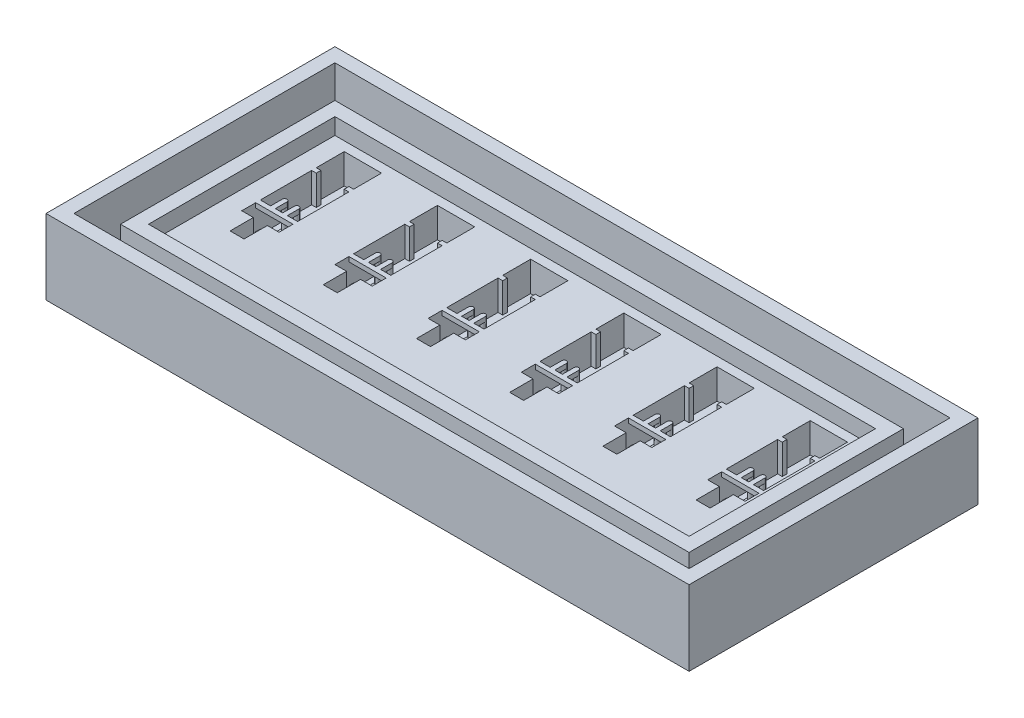
SolidWorks part; units mm, degrees
ref_plane "Front Plane" through (0, 0, 0) normal (0, 0, 1) x (1, 0, 0)
ref_plane "Top Plane" through (0, 0, 0) normal (0, 1, 0) x (1, 0, 0)
ref_plane "Right Plane" through (0, 0, 0) normal (1, 0, 0) x (0, 0, -1)
sketch "Sketch1" plane through (0, 0, 0) normal (0, 1, 0) x (1, 0, 0)
  line L1 (-30.5, -11.5) -> (30.5, -11.5)
  line L2 (-30.5, -11.5) -> (-30.5, 11.5)
  line L3 (-30.5, 11.5) -> (30.5, 11.5)
  line L4 (30.5, -11.5) -> (30.5, 11.5)
  line L5 (-30.5, -11.5) -> (30.5, 11.5) construction
  line L6 (-30.5, 11.5) -> (30.5, -11.5) construction
  point P0 (0, 0)
  dimension "D1" = 61
  dimension "D2" = 23
extrude "Boss-Extrude1" add sketch "Sketch1" along normal blind 6.05
sketch "Sketch2" plane through (0, 6.05, 0) normal (0, 1, 0) x (1, 0, 0)
  line L1 (29, -10) -> (-29, -10)
  line L2 (29, -10) -> (29, 10)
  line L3 (29, 10) -> (-29, 10)
  line L4 (-29, -10) -> (-29, 10)
  line L5 (29, -10) -> (-29, 10) construction
  line L6 (29, 10) -> (-29, -10) construction
  point P0 (0, 0)
  dimension "D1" = 58
  dimension "D2" = 20
extrude "Cut-Extrude1" cut sketch "Sketch2" against normal blind 1.75
sketch "Sketch4" plane through (0, 4.3, 0) normal (0, 1, 0) x (1, 0, 0)
  line L0 (-29, 0) -> (-28, 0) construction
  line L2 (29, -10) -> (29, 10) construction
  line L3 (-23, -0.5) -> (-22, -0.5)
  line L4 (-27, -9) -> (-23, -9)
  line L5 (-27, -9) -> (-27, -1.5)
  line L6 (-27, 9) -> (-23, 9)
  line L7 (-23, -9) -> (-23, -1.5)
  line L8 (-17, -9) -> (-13, -9)
  line L9 (-13, -9) -> (-13, -1.5)
  line L10 (-28, -1.5) -> (-27, -1.5)
  line L11 (-28, -1.5) -> (-28, -0.5)
  line L12 (-28, -0.5) -> (-27, -0.5)
  line L13 (-22, -1.5) -> (-22, -0.5)
  line L14 (-23, -1.5) -> (-22, -1.5)
  line L15 (-23, -0.5) -> (-23, 9)
  line L16 (-13, -1.5) -> (-12, -1.5)
  line L17 (-23, 0) -> (29, 0) construction
  line L18 (-12, -1.5) -> (-12, -0.5)
  line L19 (-27, -0.5) -> (-27, 9)
  line L20 (-13, -0.5) -> (-12, -0.5)
  line L21 (-13, -0.5) -> (-13, 9)
  line L22 (-17, 9) -> (-13, 9)
  line L23 (-17, -0.5) -> (-17, 9)
  line L24 (-18, -0.5) -> (-17, -0.5)
  line L25 (-18, -1.5) -> (-18, -0.5)
  line L26 (-18, -1.5) -> (-17, -1.5)
  line L27 (-17, -9) -> (-17, -1.5)
  line L28 (-7, -9) -> (-3, -9)
  line L29 (-3, -9) -> (-3, -1.5)
  line L30 (-3, -1.5) -> (-2, -1.5)
  line L31 (-2, -1.5) -> (-2, -0.5)
  line L32 (-3, -0.5) -> (-2, -0.5)
  line L33 (-3, -0.5) -> (-3, 9)
  line L34 (-7, 9) -> (-3, 9)
  line L35 (-7, -0.5) -> (-7, 9)
  line L36 (-8, -0.5) -> (-7, -0.5)
  line L37 (-8, -1.5) -> (-8, -0.5)
  line L38 (-8, -1.5) -> (-7, -1.5)
  line L39 (-7, -9) -> (-7, -1.5)
  line L40 (3, -9) -> (7, -9)
  line L41 (7, -9) -> (7, -1.5)
  line L42 (7, -1.5) -> (8, -1.5)
  line L43 (8, -1.5) -> (8, -0.5)
  line L44 (7, -0.5) -> (8, -0.5)
  line L45 (7, -0.5) -> (7, 9)
  line L46 (3, 9) -> (7, 9)
  line L47 (3, -0.5) -> (3, 9)
  line L48 (2, -0.5) -> (3, -0.5)
  line L49 (2, -1.5) -> (2, -0.5)
  line L50 (2, -1.5) -> (3, -1.5)
  line L51 (3, -9) -> (3, -1.5)
  line L52 (13, -9) -> (17, -9)
  line L53 (17, -9) -> (17, -1.5)
  line L54 (17, -1.5) -> (18, -1.5)
  line L55 (18, -1.5) -> (18, -0.5)
  line L56 (17, -0.5) -> (18, -0.5)
  line L57 (17, -0.5) -> (17, 9)
  line L58 (13, 9) -> (17, 9)
  line L59 (13, -0.5) -> (13, 9)
  line L60 (12, -0.5) -> (13, -0.5)
  line L61 (12, -1.5) -> (12, -0.5)
  line L62 (12, -1.5) -> (13, -1.5)
  line L63 (13, -9) -> (13, -1.5)
  line L64 (23, -9) -> (27, -9)
  line L65 (27, -9) -> (27, -1.5)
  line L66 (27, -1.5) -> (28, -1.5)
  line L67 (28, -1.5) -> (28, -0.5)
  line L68 (27, -0.5) -> (28, -0.5)
  line L69 (27, -0.5) -> (27, 9)
  line L70 (23, 9) -> (27, 9)
  line L71 (23, -0.5) -> (23, 9)
  line L72 (22, -0.5) -> (23, -0.5)
  line L73 (22, -1.5) -> (22, -0.5)
  line L74 (22, -1.5) -> (23, -1.5)
  line L75 (23, -9) -> (23, -1.5)
  line L76 (-27, -9) -> (-17, -9) construction
  line L77 (-25, 9) -> (-25, -9) construction
  line L78 (-29, 10) -> (-29, -10) construction
  point P6 (3, 0)
  point P11 (3, 0)
  point P85 (-25, 0)
  dimension "D1" = 4
  dimension "D2" = 18
  dimension "D3" = 6
  dimension "D4" = 1
  dimension "D6" = 10
  dimension "D7" = 1
  dimension "D8" = 9.5
  dimension "D5" = 6
extrude "Cut-Extrude3" cut sketch "Sketch4" against normal blind 3.2
sketch "Sketch5" plane through (0, 1.1, 0) normal (0, 1, 0) x (1, 0, 0)
  line L1 (-28, -0.5) -> (-22, -0.5)
  line L2 (-28, -0.5) -> (-28, -1.5)
  line L3 (-28, -1.5) -> (-22, -1.5)
  line L4 (-22, -0.5) -> (-22, -1.5)
  line L5 (-18, -0.5) -> (-12, -0.5)
  line L6 (-18, -0.5) -> (-18, -1.5)
  line L7 (-18, -1.5) -> (-12, -1.5)
  line L8 (-12, -0.5) -> (-12, -1.5)
  line L9 (-8, -0.5) -> (-2, -0.5)
  line L10 (-8, -0.5) -> (-8, -1.5)
  line L11 (-8, -1.5) -> (-2, -1.5)
  line L12 (-2, -0.5) -> (-2, -1.5)
  line L13 (2, -0.5) -> (8, -0.5)
  line L14 (2, -0.5) -> (2, -1.5)
  line L15 (2, -1.5) -> (8, -1.5)
  line L16 (8, -0.5) -> (8, -1.5)
  line L17 (12, -0.5) -> (18, -0.5)
  line L18 (12, -0.5) -> (12, -1.5)
  line L19 (12, -1.5) -> (18, -1.5)
  line L20 (18, -0.5) -> (18, -1.5)
  line L21 (22, -0.5) -> (28, -0.5)
  line L22 (22, -0.5) -> (22, -1.5)
  line L23 (22, -1.5) -> (28, -1.5)
  line L24 (28, -0.5) -> (28, -1.5)
extrude "Cut-Extrude4" cut sketch "Sketch5" against normal blind 0.5
sketch "Sketch10" plane through (0, 4.3, 0) normal (0, 1, 0) x (1, 0, 0)
  line L0 (-3, -0.5) -> (-3, 9) construction
  line L1 (-7, -0.5) -> (-3, -0.5)
  line L2 (-7, -0.5) -> (-7, 0)
  line L3 (-7, 0) -> (-3, 0)
  line L6 (-3, 0) -> (-3, -0.5)
  line L7 (23, 9) -> (23, -0.5) construction
  line L8 (23, 0) -> (27, 0)
  line L9 (23, 0) -> (23, -0.5)
  line L10 (23, -0.5) -> (27, -0.5)
  line L11 (27, 0) -> (27, -0.5)
  line L12 (27, -0.5) -> (27, 9) construction
  line L13 (13, 9) -> (13, -0.5) construction
  line L14 (13, 0) -> (17, 0)
  line L15 (13, 0) -> (13, -0.5)
  line L16 (13, -0.5) -> (17, -0.5)
  line L17 (17, 0) -> (17, -0.5)
  line L18 (17, -0.5) -> (17, 9) construction
  line L19 (3, 9) -> (3, -0.5) construction
  line L20 (3, 0) -> (7, 0)
  line L21 (3, 0) -> (3, -0.5)
  line L22 (3, -0.5) -> (7, -0.5)
  line L23 (7, 0) -> (7, -0.5)
  line L24 (7, -0.5) -> (7, 9) construction
  line L25 (-17, 9) -> (-17, -0.5) construction
  line L26 (-17, 0) -> (-13, 0)
  line L27 (-17, 0) -> (-17, -0.5)
  line L28 (-17, -0.5) -> (-13, -0.5)
  line L29 (-13, 0) -> (-13, -0.5)
  line L30 (-13, -0.5) -> (-13, 9) construction
  line L31 (-27, 9) -> (-27, -0.5) construction
  line L32 (-27, 0) -> (-23, 0)
  line L33 (-27, 0) -> (-27, -0.5)
  line L34 (-27, -0.5) -> (-23, -0.5)
  line L35 (-23, 0) -> (-23, -0.5)
  line L36 (-23, -0.5) -> (-23, 9) construction
  dimension "D1" = 0.5
extrude "Boss-Extrude3" add sketch "Sketch10" against normal blind 0.5
sketch "Sketch11" plane through (0, 1.1, 0) normal (0, 1, 0) x (1, 0, 0)
  line L0 (-3, -0.5) -> (-3, 9) construction
  line L1 (-7, -0.5) -> (-3, -0.5)
  line L2 (-7, -0.5) -> (-7, 0)
  line L3 (-7, 0) -> (-3, 0)
  line L5 (13, 9) -> (13, 0) construction
  line L6 (-3, 0) -> (-3, -0.5)
  line L7 (-27, 9) -> (-27, -0.5) construction
  line L8 (-27, 0) -> (-23, 0)
  line L9 (-27, 0) -> (-27, -0.5)
  line L10 (-27, -0.5) -> (-23, -0.5)
  line L11 (-23, 0) -> (-23, -0.5)
  line L12 (-23, 0) -> (-23, 9) construction
  line L13 (-17, 9) -> (-17, -0.5) construction
  line L14 (-17, 0) -> (-13, 0)
  line L15 (-17, 0) -> (-17, -0.5)
  line L16 (-17, -0.5) -> (-13, -0.5)
  line L17 (-13, 0) -> (-13, -0.5)
  line L18 (-13, 0) -> (-13, 9) construction
  line L19 (28, -0.5) -> (22, -0.5) construction
  line L24 (3, 9) -> (3, 0) construction
  line L25 (3, 0) -> (7, 0)
  line L26 (3, 0) -> (3, -0.5)
  line L27 (3, -0.5) -> (7, -0.5)
  line L28 (7, 0) -> (7, -0.5)
  line L29 (7, -0.5) -> (7, 9) construction
  line L30 (13, 0) -> (17, 0)
  line L31 (13, 0) -> (13, -0.5)
  line L32 (13, -0.5) -> (17, -0.5)
  line L33 (17, 0) -> (17, -0.5)
  line L34 (17, 0) -> (17, 9) construction
  line L35 (23, 0) -> (27, 0)
  line L36 (23, 0) -> (23, -0.5)
  line L37 (23, -0.5) -> (27, -0.5)
  line L38 (27, 0) -> (27, -0.5)
  line L39 (27, 0) -> (27, 9) construction
  dimension "D1" = 0.5
extrude "Boss-Extrude4" add sketch "Sketch11" along normal blind 0.5
sketch "Sketch9" plane through (0, 1.1, 0) normal (0, 1, 0) x (1, 0, 0)
  line L0 (-23, 0) -> (-27, 0) construction
  line L1 (-5.9, 1.25) -> (-5.4, 1.25)
  line L2 (-5.9, 1.25) -> (-5.9, 0)
  line L3 (-5.9, 0) -> (-5.4, 0)
  line L4 (-5.4, 1.25) -> (-5.4, 0)
  line L5 (-25.75, 0) -> (-25.25, 0)
  line L6 (-4.6, 1.25) -> (-4.1, 1.25)
  line L7 (-4.6, 1.25) -> (-4.6, 0)
  line L8 (-4.6, 0) -> (-4.1, 0)
  line L9 (-4.1, 1.25) -> (-4.1, 0)
  line L10 (-3, 0) -> (-7, 0) construction
  line L11 (-4.6, 0.625) -> (-5.4, 0.625) construction
  line L12 (-5.4, 0.625) -> (-5, 0.625) construction
  line L13 (-5, 0.625) -> (-5, 0) construction
  line L14 (-25.75, 0) -> (-25.75, 1.25)
  line L15 (-25.75, 1.25) -> (-25.25, 1.25)
  line L16 (-25.25, 0) -> (-25.25, 1.25)
  line L17 (-23, 0) -> (-27, 0) construction
  line L18 (-24.75, 0) -> (-24.25, 0)
  line L19 (-24.75, 0) -> (-24.75, 1.25)
  line L20 (-24.75, 1.25) -> (-24.25, 1.25)
  line L21 (-24.25, 0) -> (-24.25, 1.25)
  line L22 (17, 0) -> (13, 0) construction
  line L23 (13.95, 0) -> (14.45, 0)
  line L24 (13.95, 0) -> (13.95, 1.25)
  line L25 (13.95, 1.25) -> (14.45, 1.25)
  line L26 (14.45, 0) -> (14.45, 1.25)
  line L27 (-25.25, 0.625) -> (-24.75, 0.625) construction
  line L28 (15.55, 0) -> (16.05, 0)
  line L29 (15.55, 0) -> (15.55, 1.25)
  line L30 (15.55, 1.25) -> (16.05, 1.25)
  line L31 (16.05, 0) -> (16.05, 1.25)
  line L32 (-24.75, 0.625) -> (-25, 0.625) construction
  line L33 (-25, 0.625) -> (-25, 0) construction
  line L34 (14.45, 0.625) -> (15.55, 0.625) construction
  line L35 (15.55, 0.625) -> (15, 0.625) construction
  line L36 (15, 0.625) -> (15, 0) construction
  line L37 (17, 0) -> (13, 0) construction
  circle A0 centre (-4.35, 1.25) radius 0.25
  circle A1 centre (-5.65, 1.25) radius 0.25
  circle A2 centre (-25.5, 1.25) radius 0.25
  circle A3 centre (-24.5, 1.25) radius 0.25
  circle A4 centre (14.2, 1.25) radius 0.25
  circle A5 centre (15.8, 1.25) radius 0.25
  dimension "D1" = 0.5
  dimension "D2" = 1.25
  dimension "D3" = 0.8
  dimension "D4" = 0.5
  dimension "D5" = 1.1
extrude "Boss-Extrude5" add sketch "Sketch9" along normal up to surface (0.5 mm away) contours A3 L19 L18 L21 | A2 L14 L5 L16 | L15 A2 | L15 A2 | A5 L29 L28 L31 | L30 A5 | L30 A5 | L25 A4 | L25 A4 | A4 L24 L23 L26 | L2 L1 L4 L3 | A1 | A0 | L7 L6 L9 L8 | A3 region at (-25.5, 1.1, -0.5283) region at (-25.5, 1.1, -1.3561) region at (-25.5, 1.1, -1.1439) region at (-24.5, 1.1, -0.5283) region at (14.2, 1.1, -0.5283) region at (14.2, 1.1, -1.3561) region at (14.2, 1.1, -1.1439) region at (15.8, 1.1, -0.5283) region at (15.8, 1.1, -1.3561) region at (15.8, 1.1, -1.1439) up to face at (-5, 1.6, 0.25)
sketch "Sketch12" plane through (0, 4.3, 0) normal (0, 1, 0) x (1, 0, 0)
  line L10 (-7, 0) -> (-7, -0.5)
  line L11 (-7, -0.5) -> (-3, -0.5)
  line L12 (-3, -0.5) -> (-3, 0)
  line L13 (-3, 0) -> (-4.1, 0)
  line L14 (-4.1, 0) -> (-4.1, 1.25)
  line L15 (-4.6, 1.25) -> (-4.6, 0)
  line L16 (-4.6, 0) -> (-5.4, 0)
  line L17 (-5.4, 0) -> (-5.4, 1.25)
  line L18 (-5.9, 1.25) -> (-5.9, 0)
  line L19 (-5.9, 0) -> (-7, 0)
  line L20 (-7, 0) -> (-7, -0.5)
  line L21 (-7, -0.5) -> (-3, -0.5)
  line L22 (-3, -0.5) -> (-3, 0)
  line L23 (-3, 0) -> (-4.1, 0)
  line L24 (-4.1, 0) -> (-4.1, 1.25)
  line L25 (-4.6, 1.25) -> (-4.6, 0)
  line L26 (-4.6, 0) -> (-5.4, 0)
  line L27 (-5.4, 0) -> (-5.4, 1.25)
  line L28 (-5.9, 1.25) -> (-5.9, 0)
  line L29 (-5.9, 0) -> (-7, 0)
  line L30 (-27, 0) -> (-27, -0.5)
  line L31 (-27, -0.5) -> (-23, -0.5)
  line L32 (-23, -0.5) -> (-23, 0)
  line L33 (-23, 0) -> (-24.25, 0)
  line L34 (-24.25, 0) -> (-24.25, 1.25)
  line L35 (-24.75, 1.25) -> (-24.75, 0)
  line L36 (-24.75, 0) -> (-25.25, 0)
  line L37 (-25.25, 0) -> (-25.25, 1.25)
  line L38 (-25.75, 1.25) -> (-25.75, 0)
  line L39 (-25.75, 0) -> (-27, 0)
  line L40 (-27, 0) -> (-27, -0.5)
  line L41 (-27, -0.5) -> (-23, -0.5)
  line L42 (-23, -0.5) -> (-23, 0)
  line L43 (-23, 0) -> (-24.25, 0)
  line L44 (-24.25, 0) -> (-24.25, 1.25)
  line L45 (-24.75, 1.25) -> (-24.75, 0)
  line L46 (-24.75, 0) -> (-25.25, 0)
  line L47 (-25.25, 0) -> (-25.25, 1.25)
  line L48 (-25.75, 1.25) -> (-25.75, 0)
  line L49 (-25.75, 0) -> (-27, 0)
  line L50 (13, 0) -> (13, -0.5)
  line L51 (13, -0.5) -> (17, -0.5)
  line L52 (17, -0.5) -> (17, 0)
  line L53 (17, 0) -> (16.05, 0)
  line L54 (16.05, 0) -> (16.05, 1.25)
  line L55 (15.55, 1.25) -> (15.55, 0)
  line L56 (15.55, 0) -> (14.45, 0)
  line L57 (14.45, 0) -> (14.45, 1.25)
  line L58 (13.95, 1.25) -> (13.95, 0)
  line L59 (13.95, 0) -> (13, 0)
  line L60 (13, 0) -> (13, -0.5)
  line L61 (13, -0.5) -> (17, -0.5)
  line L62 (17, -0.5) -> (17, 0)
  line L63 (17, 0) -> (16.05, 0)
  line L64 (16.05, 0) -> (16.05, 1.25)
  line L65 (15.55, 1.25) -> (15.55, 0)
  line L66 (15.55, 0) -> (14.45, 0)
  line L67 (14.45, 0) -> (14.45, 1.25)
  line L68 (13.95, 1.25) -> (13.95, 0)
  line L69 (13.95, 0) -> (13, 0)
  arc A2 (-4.1, 1.25) -> (-4.6, 1.25) centre (-4.35, 1.25) ccw
  arc A3 (-5.4, 1.25) -> (-5.9, 1.25) centre (-5.65, 1.25) ccw
  arc A4 (-4.1, 1.25) -> (-4.6, 1.25) centre (-4.35, 1.25) ccw
  arc A5 (-5.4, 1.25) -> (-5.9, 1.25) centre (-5.65, 1.25) ccw
  arc A6 (-24.25, 1.25) -> (-24.75, 1.25) centre (-24.5, 1.25) ccw
  arc A7 (-25.25, 1.25) -> (-25.75, 1.25) centre (-25.5, 1.25) ccw
  arc A8 (-24.25, 1.25) -> (-24.75, 1.25) centre (-24.5, 1.25) ccw
  arc A9 (-25.25, 1.25) -> (-25.75, 1.25) centre (-25.5, 1.25) ccw
  arc A10 (16.05, 1.25) -> (15.55, 1.25) centre (15.8, 1.25) ccw
  arc A11 (14.45, 1.25) -> (13.95, 1.25) centre (14.2, 1.25) ccw
  arc A12 (16.05, 1.25) -> (15.55, 1.25) centre (15.8, 1.25) ccw
  arc A13 (14.45, 1.25) -> (13.95, 1.25) centre (14.2, 1.25) ccw
  dimension "D1" = 0
  dimension "D2" = 0
  dimension "D3" = 0
extrude "Boss-Extrude6" add sketch "Sketch12" against normal blind 0.5
sketch "Sketch13" plane through (0, 1.6, 0) normal (0, 1, 0) x (1, 0, 0)
  circle A0 centre (-5.65, 1.25) radius 0.25
  circle A1 centre (-4.35, 1.25) radius 0.25
  circle A2 centre (-25.5, 1.25) radius 0.25
  circle A3 centre (-24.5, 1.25) radius 0.25
  circle A4 centre (14.2, 1.25) radius 0.25
  circle A5 centre (15.8, 1.25) radius 0.25
extrude "Boss-Extrude7" add sketch "Sketch13" along normal up to next
sketch "Sketch14" plane through (0, 0, 0) normal (0, -1, 0) x (1, 0, 0)
  line L8 (33, -14) -> (33, 14)
  line L9 (33, 14) -> (-33, 14)
  line L10 (-33, 14) -> (-33, -14)
  line L11 (-33, -14) -> (33, -14)
  line L12 (34.5, -15.5) -> (34.5, 15.5)
  line L13 (34.5, 15.5) -> (-34.5, 15.5)
  line L14 (-34.5, 15.5) -> (-34.5, -15.5)
  line L15 (-34.5, -15.5) -> (34.5, -15.5)
  line L16 (34.5, -15.5) -> (34.5, 15.5)
  line L17 (34.5, 15.5) -> (-34.5, 15.5)
  line L18 (-34.5, 15.5) -> (-34.5, -15.5)
  line L19 (-34.5, -15.5) -> (34.5, -15.5)
  dimension "D1" = 4
  dimension "D2" = 1.5
extrude "Boss-Extrude8" add sketch "Sketch14" against normal offset from surface (7.05 mm away) 1 separate body up to face at (0, 6.05, 0) offset beyond the face yes
sketch "Sketch15" plane through (0, 0, 0) normal (0, -1, 0) x (1, 0, 0)
  line L1 (33, 14) -> (-33, 14)
  line L2 (33, 14) -> (33, -14)
  line L3 (33, -14) -> (-33, -14)
  line L4 (-34.5, -15.5) -> (34.5, -15.5)
  line L5 (34.5, -15.5) -> (34.5, 15.5)
  line L6 (34.5, 15.5) -> (-34.5, 15.5)
  line L7 (-34.5, 15.5) -> (-34.5, -15.5)
  line L8 (-34.5, -15.5) -> (34.5, -15.5)
  line L9 (34.5, -15.5) -> (34.5, 15.5)
  line L10 (34.5, 15.5) -> (-34.5, 15.5)
  line L11 (-34.5, 15.5) -> (-34.5, -15.5)
  line L12 (-33, 14) -> (-33, -14)
  dimension "D1" = 0
extrude "Boss-Extrude9" add sketch "Sketch15" along normal blind 1
pattern_linear "LPattern1" count 2 spacing 10 along (1, 0, 0) of "Boss-Extrude6", "Boss-Extrude7", "Boss-Extrude5"
sketch "Sketch16" plane through (0, 4.3, 0) normal (0, 1, 0) x (1, 0, 0)
  line L0 (-27, -1.5) -> (-27, -0.5)
  line L1 (-28, -0.5) -> (-27, -0.5)
  line L2 (-28, -0.5) -> (-28, -1.5)
  line L3 (-28, -1.5) -> (-27, -1.5)
  line L4 (-22, -0.5) -> (-22, -1.5)
  line L5 (-18, -0.5) -> (-17, -0.5)
  line L6 (-18, -0.5) -> (-18, -1.5)
  line L7 (-18, -1.5) -> (-17, -1.5)
  line L8 (-12, -0.5) -> (-12, -1.5)
  line L9 (-8, -0.5) -> (-7, -0.5)
  line L10 (-8, -0.5) -> (-8, -1.5)
  line L11 (-8, -1.5) -> (-7, -1.5)
  line L12 (-2, -0.5) -> (-2, -1.5)
  line L13 (2, -0.5) -> (3, -0.5)
  line L14 (2, -0.5) -> (2, -1.5)
  line L15 (2, -1.5) -> (3, -1.5)
  line L16 (8, -0.5) -> (8, -1.5)
  line L17 (12, -0.5) -> (13, -0.5)
  line L18 (12, -0.5) -> (12, -1.5)
  line L19 (12, -1.5) -> (13, -1.5)
  line L20 (18, -0.5) -> (18, -1.5)
  line L21 (22, -0.5) -> (23, -0.5)
  line L22 (22, -0.5) -> (22, -1.5)
  line L23 (22, -1.5) -> (23, -1.5)
  line L24 (28, -0.5) -> (28, -1.5)
  line L25 (-23, -1.5) -> (-23, -0.5)
  line L26 (-17, -1.5) -> (-17, -0.5)
  line L27 (-13, -1.5) -> (-13, -0.5)
  line L28 (-7, -1.5) -> (-7, -0.5)
  line L29 (-3, -1.5) -> (-3, -0.5)
  line L30 (3, -1.5) -> (3, -0.5)
  line L31 (7, -1.5) -> (7, -0.5)
  line L32 (13, -1.5) -> (13, -0.5)
  line L33 (17, -1.5) -> (17, -0.5)
  line L34 (23, -1.5) -> (23, -0.5)
  line L35 (27, -1.5) -> (27, -0.5)
  line L36 (-23, -0.5) -> (-22, -0.5)
  line L37 (-23, -1.5) -> (-22, -1.5)
  line L38 (-13, -0.5) -> (-12, -0.5)
  line L39 (-13, -1.5) -> (-12, -1.5)
  line L40 (-3, -0.5) -> (-2, -0.5)
  line L41 (-3, -1.5) -> (-2, -1.5)
  line L42 (7, -0.5) -> (8, -0.5)
  line L43 (7, -1.5) -> (8, -1.5)
  line L44 (17, -0.5) -> (18, -0.5)
  line L45 (17, -1.5) -> (18, -1.5)
  line L46 (27, -0.5) -> (28, -0.5)
  line L47 (27, -1.5) -> (28, -1.5)
extrude "Boss-Extrude11" add sketch "Sketch16" against normal up to next
sketch "Sketch18" plane through (0, 1.1, 0) normal (0, 1, 0) x (1, 0, 0)
  line L1 (-27, -1.5) -> (-23, -1.5)
  line L2 (-27, -1.5) -> (-27, -0.5)
  line L3 (-27, -0.5) -> (-23, -0.5)
  line L4 (-23, -1.5) -> (-23, -0.5)
  line L5 (-17, -1.5) -> (-13, -1.5)
  line L6 (-17, -1.5) -> (-17, -0.5)
  line L7 (-17, -0.5) -> (-13, -0.5)
  line L8 (-13, -1.5) -> (-13, -0.5)
  line L9 (-7, -1.5) -> (-3, -1.5)
  line L10 (-7, -1.5) -> (-7, -0.5)
  line L11 (-7, -0.5) -> (-3, -0.5)
  line L12 (-3, -1.5) -> (-3, -0.5)
  line L13 (3, -1.5) -> (7, -1.5)
  line L14 (3, -1.5) -> (3, -0.5)
  line L15 (3, -0.5) -> (7, -0.5)
  line L16 (7, -1.5) -> (7, -0.5)
  line L17 (13, -1.5) -> (17, -1.5)
  line L18 (13, -1.5) -> (13, -0.5)
  line L19 (13, -0.5) -> (17, -0.5)
  line L20 (17, -1.5) -> (17, -0.5)
  line L21 (23, -1.5) -> (27, -1.5)
  line L22 (23, -1.5) -> (23, -0.5)
  line L23 (23, -0.5) -> (27, -0.5)
  line L24 (27, -1.5) -> (27, -0.5)
extrude "Boss-Extrude12" add sketch "Sketch18" against normal up to next
sketch "Sketch19" plane through (0, 0, 11.5) normal (0, 0, 1) x (1, 0, 0)
  line L0 (30.5, 6.05) -> (30.5, 0) construction
  line L1 (-30.5, 0) -> (30.5, 0)
  line L2 (-30.5, 0) -> (-30.5, 0.5)
  line L3 (-30.5, 0.5) -> (30.5, 0.5)
  line L4 (30.5, 0) -> (30.5, 0.5)
  dimension "D1" = 0.5
extrude "Cut-Extrude5" cut sketch "Sketch19" against normal up to next (23 mm away)
sketch "Sketch20" plane through (0, 4.3, 0) normal (0, 1, 0) x (1, 0, 0)
  line L0 (27, -9) -> (27, -0.5) construction
  line L1 (-27, -9) -> (27, -9)
  line L2 (-27, -9) -> (-27, -2)
  line L3 (-27, -2) -> (27, -2)
  line L4 (27, -9) -> (27, -2)
  dimension "D1" = 7
extrude "Boss-Extrude13" add sketch "Sketch20" against normal up to surface (3.2 mm away) up to face at (-25, 1.1, -1.9583)
sketch "Sketch21" plane through (0, 4.3, 0) normal (0, 1, 0) x (1, 0, 0)
  line L0 (-23, -2) -> (-27, -2) construction
  line L1 (-25.75, -2) -> (-24.25, -2)
  line L2 (-25.75, -2) -> (-25.75, -4.5)
  line L3 (-25.75, -4.5) -> (-24.25, -4.5)
  line L4 (-24.25, -2) -> (-24.25, -4.5)
  point P6 (-25, -2)
  dimension "D1" = 1.5
  dimension "1.5" = 2.5
extrude "Cut-Extrude6" cut sketch "Sketch21" against normal up to surface (3.2 mm away) up to face at (-25, 1.1, -1.9583)
sketch "Sketch22" plane through (0, 4.3, 0) normal (0, 1, 0) x (1, 0, 0)
  line L0 (-27, 9) -> (-27, 0) construction
  line L1 (-23, 0) -> (-23, 9) construction
  line L2 (-27, 6) -> (-26.5, 6)
  line L3 (-27, 6) -> (-27, 5.5)
  line L4 (-27, 5.5) -> (-26.5, 5.5)
  line L5 (-26.5, 6) -> (-26.5, 5.5)
  line L6 (-23, 6) -> (-23.5, 6)
  line L7 (-23, 6) -> (-23, 5.5)
  line L8 (-23, 5.5) -> (-23.5, 5.5)
  line L9 (-23.5, 6) -> (-23.5, 5.5)
  line L10 (-23, 9) -> (-27, 9) construction
  arc A0 (-25.25, 1.25) -> (-25.75, 1.25) centre (-25.5, 1.25) ccw construction
  point P0 (-25.5, 1.5)
  point P1 (-27, 6)
  dimension "D1" = 3
  dimension "D2" = 0.5
  dimension "D3" = 0.5
extrude "Boss-Extrude14" add sketch "Sketch22" against normal up to next
pattern_linear "LPattern2" count 6 spacing 10 along (1, 0, 0) of "Cut-Extrude6", "Boss-Extrude14"
sketch "Sketch23" plane through (0, 4.3, 0) normal (0, 1, 0) x (1, 0, 0)
  line L0 (-17, 5.5) -> (-17, 0) construction
  line L1 (-13, 0) -> (-17, 0)
  line L2 (-13, 0) -> (-13, 2.75)
  line L3 (-13, 2.75) -> (-17, 2.75)
  line L4 (-17, 0) -> (-17, 2.75)
  line L5 (-23, 0) -> (-23, 5.5) construction
  line L6 (-23, 0) -> (-27, 0)
  line L7 (-23, 0) -> (-23, 2.75)
  line L8 (-23, 2.75) -> (-27, 2.75)
  line L9 (-27, 0) -> (-27, 2.75)
  line L10 (-27, 5.5) -> (-27, 0) construction
  line L11 (17, 0) -> (17, 5.5) construction
  line L12 (13, 0) -> (17, 0)
  line L13 (13, 0) -> (13, 2.75)
  line L14 (13, 2.75) -> (17, 2.75)
  line L15 (17, 0) -> (17, 2.75)
  line L16 (27, 0) -> (27, 5.5) construction
  line L17 (23, 0) -> (27, 0)
  line L18 (23, 0) -> (23, 2.75)
  line L19 (23, 2.75) -> (27, 2.75)
  line L20 (27, 0) -> (27, 2.75)
extrude "Cut-Extrude7" cut sketch "Sketch23" against normal up to surface (3.2 mm away) up to face at (-25, 1.1, -3.475)
sketch "Sketch24" plane through (0, 1.1, 0) normal (0, 1, 0) x (1, 0, 0)
  line L0 (-23, 0) -> (-27, 0) construction
  line L1 (-25.9, 0) -> (-25.4, 0)
  line L2 (-25.9, 0) -> (-25.9, 1.25)
  line L3 (-25.9, 1.25) -> (-25.4, 1.25)
  line L4 (-25.4, 0) -> (-25.4, 1.25)
  line L5 (-23, 0) -> (-27, 0) construction
  line L6 (-24.6, 0) -> (-24.1, 0)
  line L7 (-24.6, 0) -> (-24.6, 1.25)
  line L8 (-24.6, 1.25) -> (-24.1, 1.25)
  line L9 (-24.1, 0) -> (-24.1, 1.25)
  line L12 (-25.4, 0.625) -> (-24.6, 0.625) construction
  line L13 (-24.6, 0.625) -> (-25, 0.625) construction
  line L14 (-25, 0.625) -> (-25, 0) construction
  circle A0 centre (-25.65, 1.25) radius 0.25
  circle A1 centre (-24.35, 1.25) radius 0.25
  arc A2 (-5.4, 1.25) -> (-5.9, 1.25) centre (-5.65, 1.25) ccw construction
  line M9 (-27, 0) -> (-23, 0)
  dimension "D1" = 1.25
  dimension "D2" = 0.8
extrude "Boss-Extrude15" add sketch "Sketch24" along normal up to surface (0.5 mm away) contours A1 L7 L9 M9 | L8 A1 | L8 A1 | L3 A0 | L3 A0 | A0 L2 L4 M9 region at (-25.65, 1.1, -0.5283) region at (-24.35, 1.1, -0.5283) region at (-25.65, 1.1, -1.3561) region at (-25.65, 1.1, -1.1439) region at (-24.35, 1.1, -1.3561) region at (-24.35, 1.1, -1.1439) up to face at (-5, 1.6, -0.2917)
ref_plane "Plane1" through (0, 2.7, 0) normal (0, 1, 0) x (1, 0, 0)
sketch "Sketch25" plane through (0, 4.3, 0) normal (0, 1, 0) x (1, 0, 0)
  line L4 (-25.9, 0) -> (-25.4, 0)
  line L5 (-25.4, 0) -> (-25.4, 1.25)
  line L6 (-25.4, 1.25) -> (-25.9, 1.25)
  line L7 (-25.9, 1.25) -> (-25.9, 0)
  line L8 (-25.9, 0) -> (-25.4, 0)
  line L9 (-25.4, 0) -> (-25.4, 1.25)
  line L10 (-25.4, 1.25) -> (-25.9, 1.25)
  line L11 (-25.9, 1.25) -> (-25.9, 0)
  line L12 (-24.6, 0) -> (-24.1, 0)
  line L13 (-24.6, 1.25) -> (-24.6, 0)
  line L14 (-24.1, 1.25) -> (-24.6, 1.25)
  line L15 (-24.1, 0) -> (-24.1, 1.25)
  line L16 (-24.6, 0) -> (-24.1, 0)
  line L17 (-24.6, 1.25) -> (-24.6, 0)
  line L18 (-24.1, 1.25) -> (-24.6, 1.25)
  line L19 (-24.1, 0) -> (-24.1, 1.25)
  circle A1 centre (-24.35, 1.25) radius 0.25
  circle A2 centre (-24.35, 1.25) radius 0.25
  circle A3 centre (-25.65, 1.25) radius 0.25
  circle A4 centre (-25.65, 1.25) radius 0.25
  dimension "D1" = 0
  dimension "D2" = 0
  dimension "D3" = 0
  dimension "D4" = 0
extrude "Boss-Extrude16" add sketch "Sketch25" against normal blind 0.5 contours A4 L11 L8 L9 | L10 A4 | L10 A4 | L18 A2 | L18 A2 | A2 L17 L16 L19 region at (-25.65, 4.3, -0.5283) region at (-25.65, 4.3, -1.3561) region at (-25.65, 4.3, -1.1439) region at (-24.35, 4.3, -0.5283) region at (-24.35, 4.3, -1.3561) region at (-24.35, 4.3, -1.1439)
sketch "Sketch26" plane through (0, 1.6, 0) normal (0, 1, 0) x (1, 0, 0)
  circle A0 centre (-25.65, 1.25) radius 0.25
  circle A1 centre (-24.35, 1.25) radius 0.25
  arc A2 (-24.1, 1.25) -> (-24.6, 1.25) centre (-24.35, 1.25) ccw construction
extrude "Boss-Extrude17" add sketch "Sketch26" along normal up to next
pattern_linear "LPattern5" count 6 spacing 10 along (1, 0, 0) of "Boss-Extrude15", "Boss-Extrude16", "Boss-Extrude17"
